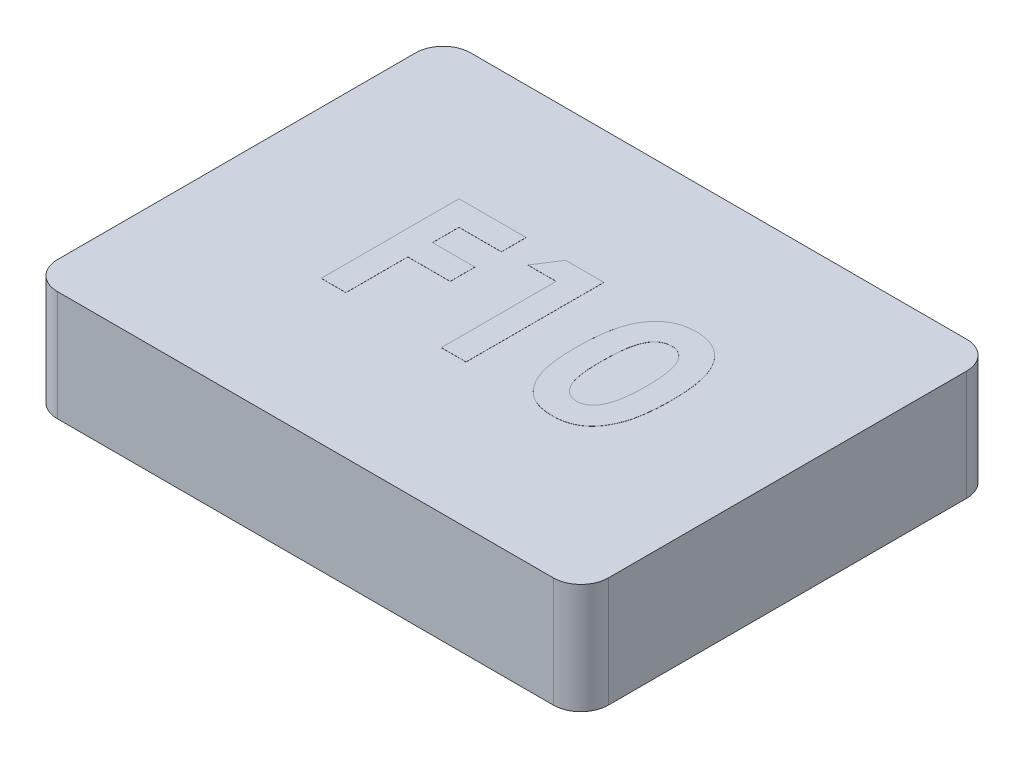
SolidWorks part; units mm, degrees
ref_plane "Front Plane" through (0, 0, 0) normal (0, 0, 1) x (1, 0, 0)
ref_plane "Top Plane" through (0, 0, 0) normal (0, 1, 0) x (1, 0, 0)
ref_plane "Right Plane" through (0, 0, 0) normal (1, 0, 0) x (0, 0, -1)
sketch "Sketch1" plane through (0, 0, 0) normal (0, 1, 0) x (1, 0, 0)
  line L0 (0, 0) -> (12.7, 0)
  line L1 (12.7, 0) -> (12.7, 9.525)
  line L2 (12.7, 9.525) -> (0, 9.525)
  line L3 (0, 9.525) -> (0, 0)
  dimension "D1" = 12.7
  dimension "D2" = 9.525
extrude "Boss-Extrude1" add sketch "Sketch1" along normal blind 2.54
fillet "Fillet1" radius 0.635 4 edges at (0, 1.27, -9.525) (12.7, 1.27, -9.525) (12.7, 1.27, 0) (0, 1.27, 0)
shell "Shell1" thickness 0.635 removed face at (6.35, 0, -4.7625)
sketch "Sketch2" plane through (0, 1.905, 0) normal (0, -1, 0) x (-1, 0, 0)
  line L0 (-0.635, 4.7625) -> (-12.065, 4.7625) construction
  line L1 (-0.635, 8.89) -> (-0.635, 0.635) construction
  line L2 (-12.065, 0.635) -> (-12.065, 8.89) construction
  line L3 (-6.35, 0.635) -> (-6.35, 8.89) construction
  line L4 (-0.635, 0.635) -> (-12.065, 0.635) construction
  line L5 (-12.065, 8.89) -> (-0.635, 8.89) construction
  circle A0 centre (-6.35, 4.7625) radius 2.54
  dimension "D1" = 5.08
extrude "Boss-Extrude2" add sketch "Sketch2" along normal up to surface (1.905 mm away) up to face at (6.35, 0, -4.7625)
sketch "Sketch3" plane through (0, 2.54, 0) normal (0, 1, 0) x (1, 0, 0)
  line L0 (0.635, 0) -> (12.065, 0) construction
  line L1 (0, 8.89) -> (0, 0.635) construction
  text T0 "<b>F10</b>"
  dimension "D1" = 3.302
  dimension "D2" = 3.048
extrude "Boss-Extrude3" add sketch "Sketch3" along normal blind 0.0025
